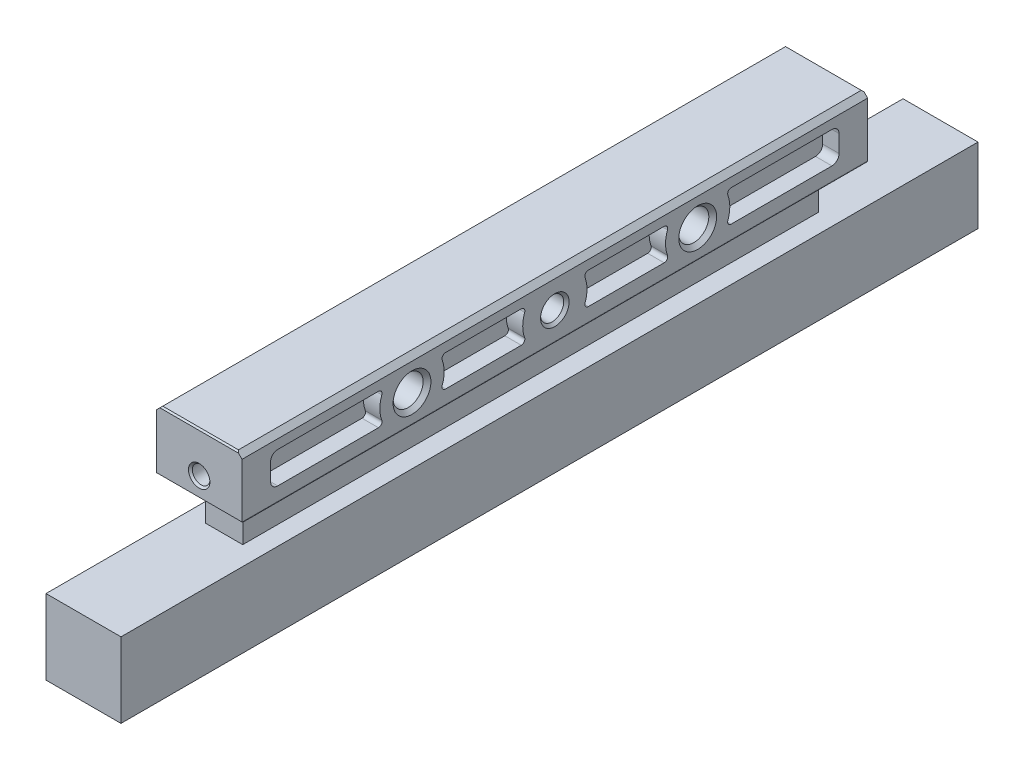
SolidWorks part; units mm, degrees
ref_plane "Front Plane" through (0, 0, 0) normal (0, 0, 1) x (1, 0, 0)
ref_plane "Top Plane" through (0, 0, 0) normal (0, 1, 0) x (1, 0, 0)
ref_plane "Right Plane" through (0, 0, 0) normal (1, 0, 0) x (0, 0, -1)
sketch "Sketch1" plane through (0, 0, 0) normal (0, 0, 1) x (1, 0, 0)
  line L0 (-5.8, 16.5) -> (-2.9, 16.5)
  line L1 (-2.6, 16.2) -> (-2.6, 10.5)
  line L2 (-2.6, 10.5) -> (-5.25, 10.5)
  line L3 (-5.25, 10.5) -> (-5.25, 0)
  line L4 (-5.25, 0) -> (5.25, 0)
  line L5 (5.25, 0) -> (5.25, 10.5)
  line L6 (5.25, 10.5) -> (2.6, 10.5)
  line L7 (2.6, 10.5) -> (2.6, 16.2)
  line L8 (2.9, 16.5) -> (5.8, 16.5)
  line L9 (6, 16.7) -> (6, 24.3)
  line L10 (6, 24.3) -> (5.3, 25)
  line L11 (5.3, 25) -> (-5.3, 25)
  line L12 (-5.3, 25) -> (-6, 24.3)
  line L13 (-6, 24.3) -> (-6, 16.7)
  arc A0 (-6, 16.7) -> (-5.8, 16.5) centre (-5.8, 16.7) ccw
  arc A1 (-2.9, 16.5) -> (-2.6, 16.2) centre (-2.9, 16.2) cw
  arc A2 (2.6, 16.2) -> (2.9, 16.5) centre (2.9, 16.2) cw
  arc A3 (5.8, 16.5) -> (6, 16.7) centre (5.8, 16.7) ccw
extrude "Boss-Extrude1" add sketch "Sketch1" against normal blind 60 and the other way blind 60
sketch "Sketch2" plane through (0, 0, 0) normal (1, 0, 0) x (0, 0, -1)
  line L0 (-65, 30) -> (-65, 10.5)
  line L1 (-65, 10.5) -> (-40.3, 10.5)
  line L2 (-40.3, 10.5) -> (-40.3, 16.2)
  line L3 (-40.6, 16.5) -> (-43.6, 16.5)
  line L4 (-43.6, 16.5) -> (-43.8, 16.7)
  line L5 (-43.8, 16.7) -> (-43.8, 24.8)
  line L6 (-43.8, 24.8) -> (-43.6, 25)
  line L7 (-43.6, 25) -> (43.6, 25)
  line L8 (43.6, 25) -> (43.8, 24.8)
  line L9 (43.8, 24.8) -> (43.8, 16.7)
  line L10 (43.8, 16.7) -> (43.6, 16.5)
  line L11 (43.6, 16.5) -> (40.6, 16.5)
  line L12 (40.3, 16.2) -> (40.3, 10.5)
  line L13 (40.3, 10.5) -> (65, 10.5)
  line L14 (65, 10.5) -> (65, 30)
  line L15 (65, 30) -> (-65, 30)
  arc A0 (-40.3, 16.2) -> (-40.6, 16.5) centre (-40.6, 16.2) ccw
  arc A1 (40.6, 16.5) -> (40.3, 16.2) centre (40.6, 16.2) ccw
extrude "Cut-Extrude1" cut sketch "Sketch2" along normal blind 12 and the other way blind 12
sketch "Sketch3" plane through (0, 0, 0) normal (0, 0, 1) x (1, 0, 0)
  line L0 (-6, 20.5) -> (-6, 22.5)
  line L1 (-6, 22.5) -> (-5.621, 22.121)
  line L2 (-5.621, 22.121) -> (5.621, 22.121)
  line L3 (5.621, 22.121) -> (6, 22.5)
  line L4 (6, 22.5) -> (6, 20.5)
  line L5 (6, 20.5) -> (-6, 20.5)
  line L6 (6, 20.5) -> (-6, 20.5) construction
revolve "Cut-Revolve1" cut sketch "Sketch3" angle 360 about L6 reverse direction yes
cosmetic thread "Cosmetic Thread1" parameters "D1"=12, "D2"=4
ref_plane "Plane1" through (0, 0, 20) normal (0, 0, 1) x (1, 0, 0)
sketch "Sketch4" plane through (0, 0, 20) normal (0, 0, 1) x (1, 0, 0)
  line L0 (-6, 20.5) -> (-6, 23.15)
  line L1 (-6, 23.15) -> (-5.4548, 22.6)
  line L2 (-5.4548, 22.6) -> (5.4548, 22.6)
  line L3 (5.4548, 22.6) -> (6, 23.15)
  line L4 (6, 23.15) -> (6, 20.5)
  line L5 (6, 20.5) -> (-6, 20.5)
  line L6 (0, 20.5) -> (-6, 20.5) construction
revolve "Cut-Revolve2" cut sketch "Sketch4" angle 360 about L6 reverse direction yes
ref_plane "Plane2" through (0, 0, -20) normal (0, 0, 1) x (1, 0, 0)
sketch "Sketch5" plane through (0, 0, -20) normal (0, 0, 1) x (1, 0, 0)
  line L0 (-6, 20.5) -> (-6, 23.15)
  line L1 (-6, 23.15) -> (-5.4548, 22.6)
  line L2 (-5.4548, 22.6) -> (5.4548, 22.6)
  line L3 (5.4548, 22.6) -> (6, 23.15)
  line L4 (6, 23.15) -> (6, 20.5)
  line L5 (6, 20.5) -> (-6, 20.5)
  line L6 (0, 20.5) -> (-6, 20.5) construction
revolve "Cut-Revolve3" cut sketch "Sketch5" angle 360 about L6 reverse direction yes
sketch "Sketch6" plane through (0, 0, 0) normal (1, 0, 0) x (0, 0, -1)
  line L0 (-43.8, 19.3) -> (-43.8, 20.8)
  line L1 (-43.8, 20.8) -> (-43.5295, 20.5295)
  line L2 (-43.5295, 20.5295) -> (-33.3, 20.5295)
  line L3 (-33.3, 20.5295) -> (-32.5901, 19.3)
  line L4 (-32.5901, 19.3) -> (-43.8, 19.3)
  line L5 (-32.5901, 19.3) -> (-43.8, 19.3) construction
revolve "Cut-Revolve4" cut sketch "Sketch6" angle 360 about L5 reverse direction yes
cosmetic thread "Cosmetic Thread2" parameters "D1"=8.5, "D2"=3
ref_plane "Plane3" through (6, 0, 0) normal (1, 0, 0) x (0, 0, -1)
sketch "Sketch7" plane through (6, 0, 0) normal (1, 0, 0) x (0, 0, -1)
  line L0 (24.6985, 18.58) -> (38.8, 18.58)
  line L1 (39.8, 19.58) -> (39.8, 22)
  line L2 (38.8, 23) -> (24.6985, 23)
  arc A0 (24.2286, 19.251) -> (24.6985, 18.58) centre (24.6985, 19.08) ccw
  arc A1 (38.8, 18.58) -> (39.8, 19.58) centre (38.8, 19.58) ccw
  arc A2 (39.8, 22) -> (38.8, 23) centre (38.8, 22) ccw
  arc A3 (24.6985, 23) -> (24.2286, 22.329) centre (24.6985, 22.5) ccw
  arc A4 (24.2286, 22.329) -> (24.2286, 19.251) centre (20, 20.79) cw
extrude "Cut-Extrude2" cut sketch "Sketch7" against normal blind 2.3
sketch "Sketch8" plane through (6, 0, 0) normal (1, 0, 0) x (0, 0, -1)
  line L0 (-39.8, 22) -> (-39.8, 19.58)
  line L1 (-38.8, 18.58) -> (-24.6985, 18.58)
  line L2 (-24.6985, 23) -> (-38.8, 23)
  arc A0 (-39.8, 19.58) -> (-38.8, 18.58) centre (-38.8, 19.58) ccw
  arc A1 (-24.6985, 18.58) -> (-24.2286, 19.251) centre (-24.6985, 19.08) ccw
  arc A2 (-24.2286, 19.251) -> (-24.2286, 22.329) centre (-20, 20.79) cw
  arc A3 (-24.2286, 22.329) -> (-24.6985, 23) centre (-24.6985, 22.5) ccw
  arc A4 (-38.8, 23) -> (-39.8, 22) centre (-38.8, 22) ccw
extrude "Cut-Extrude3" cut sketch "Sketch8" against normal blind 2.3
sketch "Sketch9" plane through (6, 0, 0) normal (1, 0, 0) x (0, 0, -1)
  line L0 (4.6985, 18.58) -> (15.3015, 18.58)
  line L1 (15.3015, 23) -> (4.6985, 23)
  arc A0 (4.6985, 23) -> (4.2286, 22.329) centre (4.6985, 22.5) ccw
  arc A1 (4.2286, 22.329) -> (4.2286, 19.251) centre (0, 20.79) cw
  arc A2 (4.2286, 19.251) -> (4.6985, 18.58) centre (4.6985, 19.08) ccw
  arc A3 (15.3015, 18.58) -> (15.7714, 19.251) centre (15.3015, 19.08) ccw
  arc A4 (15.7714, 19.251) -> (15.7714, 22.329) centre (20, 20.79) cw
  arc A5 (15.7714, 22.329) -> (15.3015, 23) centre (15.3015, 22.5) ccw
extrude "Cut-Extrude4" cut sketch "Sketch9" against normal blind 2.3
sketch "Sketch10" plane through (6, 0, 0) normal (1, 0, 0) x (0, 0, -1)
  line L0 (-15.3015, 18.58) -> (-4.6985, 18.58)
  line L1 (-4.6985, 23) -> (-15.3015, 23)
  arc A0 (-15.7714, 19.251) -> (-15.3015, 18.58) centre (-15.3015, 19.08) ccw
  arc A1 (-4.6985, 18.58) -> (-4.2286, 19.251) centre (-4.6985, 19.08) ccw
  arc A2 (-4.2286, 19.251) -> (-4.2286, 22.329) centre (0, 20.79) cw
  arc A3 (-4.2286, 22.329) -> (-4.6985, 23) centre (-4.6985, 22.5) ccw
  arc A4 (-15.3015, 23) -> (-15.7714, 22.329) centre (-15.3015, 22.5) ccw
  arc A5 (-15.7714, 22.329) -> (-15.7714, 19.251) centre (-20, 20.79) cw
extrude "Cut-Extrude5" cut sketch "Sketch10" against normal blind 2.3
ref_plane "Plane4" through (-6, 0, 0) normal (1, 0, 0) x (0, 0, -1)
sketch "Sketch11" plane through (-6, 0, 0) normal (1, 0, 0) x (0, 0, -1)
  line L0 (24.6985, 18.58) -> (38.8, 18.58)
  line L1 (39.8, 19.58) -> (39.8, 22)
  line L2 (38.8, 23) -> (24.6985, 23)
  arc A0 (24.2286, 19.251) -> (24.6985, 18.58) centre (24.6985, 19.08) ccw
  arc A1 (38.8, 18.58) -> (39.8, 19.58) centre (38.8, 19.58) ccw
  arc A2 (39.8, 22) -> (38.8, 23) centre (38.8, 22) ccw
  arc A3 (24.6985, 23) -> (24.2286, 22.329) centre (24.6985, 22.5) ccw
  arc A4 (24.2286, 22.329) -> (24.2286, 19.251) centre (20, 20.79) cw
extrude "Cut-Extrude6" cut sketch "Sketch11" along normal blind 2.3
sketch "Sketch12" plane through (-6, 0, 0) normal (1, 0, 0) x (0, 0, -1)
  line L0 (-39.8, 22) -> (-39.8, 19.58)
  line L1 (-38.8, 18.58) -> (-24.6985, 18.58)
  line L2 (-24.6985, 23) -> (-38.8, 23)
  arc A0 (-39.8, 19.58) -> (-38.8, 18.58) centre (-38.8, 19.58) ccw
  arc A1 (-24.6985, 18.58) -> (-24.2286, 19.251) centre (-24.6985, 19.08) ccw
  arc A2 (-24.2286, 19.251) -> (-24.2286, 22.329) centre (-20, 20.79) cw
  arc A3 (-24.2286, 22.329) -> (-24.6985, 23) centre (-24.6985, 22.5) ccw
  arc A4 (-38.8, 23) -> (-39.8, 22) centre (-38.8, 22) ccw
extrude "Cut-Extrude7" cut sketch "Sketch12" along normal blind 2.3
sketch "Sketch13" plane through (-6, 0, 0) normal (1, 0, 0) x (0, 0, -1)
  line L0 (4.6985, 18.58) -> (15.3015, 18.58)
  line L1 (15.3015, 23) -> (4.6985, 23)
  arc A0 (4.6985, 23) -> (4.2286, 22.329) centre (4.6985, 22.5) ccw
  arc A1 (4.2286, 22.329) -> (4.2286, 19.251) centre (0, 20.79) cw
  arc A2 (4.2286, 19.251) -> (4.6985, 18.58) centre (4.6985, 19.08) ccw
  arc A3 (15.3015, 18.58) -> (15.7714, 19.251) centre (15.3015, 19.08) ccw
  arc A4 (15.7714, 19.251) -> (15.7714, 22.329) centre (20, 20.79) cw
  arc A5 (15.7714, 22.329) -> (15.3015, 23) centre (15.3015, 22.5) ccw
extrude "Cut-Extrude8" cut sketch "Sketch13" along normal blind 2.3
sketch "Sketch14" plane through (-6, 0, 0) normal (1, 0, 0) x (0, 0, -1)
  line L0 (-15.3015, 18.58) -> (-4.6985, 18.58)
  line L1 (-4.6985, 23) -> (-15.3015, 23)
  arc A0 (-15.7714, 19.251) -> (-15.3015, 18.58) centre (-15.3015, 19.08) ccw
  arc A1 (-4.6985, 18.58) -> (-4.2286, 19.251) centre (-4.6985, 19.08) ccw
  arc A2 (-4.2286, 19.251) -> (-4.2286, 22.329) centre (0, 20.79) cw
  arc A3 (-4.2286, 22.329) -> (-4.6985, 23) centre (-4.6985, 22.5) ccw
  arc A4 (-15.3015, 23) -> (-15.7714, 22.329) centre (-15.3015, 22.5) ccw
  arc A5 (-15.7714, 22.329) -> (-15.7714, 19.251) centre (-20, 20.79) cw
extrude "Cut-Extrude9" cut sketch "Sketch14" along normal blind 2.3
ref_plane "ANBAU XY" through (0, 0, 0) normal (0, 0, 1) x (1, 0, 0)
ref_plane "ANBAU XZ" through (0, 5.25, 0) normal (0, -1, 0) x (-1, 0, 0)
ref_plane "ANBAU YZ" through (0, 0, 0) normal (1, 0, 0) x (0, 0, -1)
ref_axis "ANBAU X" through (-80.9, 5.25, 0) along (1, 0, 0)
ref_axis "ANBAU Y" through (0, -50, 0) along (0, 1, 0)
ref_axis "ANBAU Z" through (0, 5.25, 80.9) along (0, 0, -1)
sketch3d "ANBAU"
  point P0 (0, 5.25, 0)
ref_plane "L3_2 XY" through (0, 0, 0) normal (1, 0, 0) x (0, 0, -1)
ref_plane "L3_2 XZ" through (0, 25, 0) normal (0, -1, 0) x (-1, 0, 0)
ref_plane "L3_2 YZ" through (0, 0, 43.8) normal (0, 0, -1) x (-1, 0, 0)
ref_axis "L3_2 X" through (0, 25, 80.9) along (0, 0, -1)
ref_axis "L3_2 Y" through (0, -50, 43.8) along (0, 1, 0)
ref_axis "L3_2 Z" through (80.9, 25, 43.8) along (-1, 0, 0)
sketch3d "L3_2"
  point P0 (0, 25, 43.8)
ref_plane "TO_BRIDGE XY" through (0, 0, 0) normal (0, 0, -1) x (-1, 0, 0)
ref_plane "TO_BRIDGE XZ" through (0, 19.3, 0) normal (0, 1, 0) x (1, 0, 0)
ref_plane "TO_BRIDGE YZ" through (0, 0, 0) normal (1, 0, 0) x (0, 0, -1)
ref_axis "TO_BRIDGE X" through (-80.9, 19.3, 0) along (1, 0, 0)
ref_axis "TO_BRIDGE Y" through (0, 50, 0) along (0, -1, 0)
ref_axis "TO_BRIDGE Z" through (0, 19.3, -80.9) along (0, 0, 1)
sketch3d "TO_BRIDGE"
  point P0 (0, 19.3, 0)
other "Freeze***"
